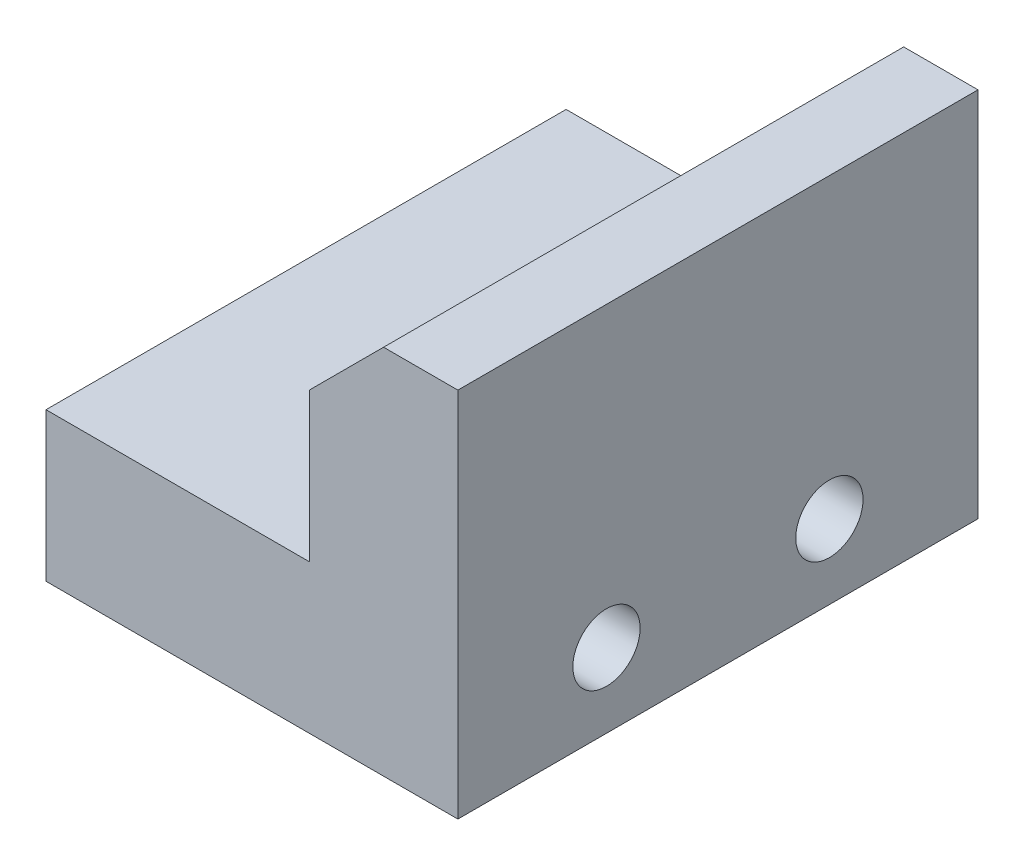
SolidWorks part; units mm, degrees
material "PETG"
ref_plane "Front Plane" through (0, 0, 0) normal (0, 0, 1) x (1, 0, 0)
ref_plane "Top Plane" through (0, 0, 0) normal (0, 1, 0) x (1, 0, 0)
ref_plane "Right Plane" through (0, 0, 0) normal (1, 0, 0) x (0, 0, -1)
sketch "Sketch1" plane through (0, 0, 0) normal (0, 0, 1) x (1, 0, 0)
  line L0 (70.4, 63.5) -> (45, 38.1)
  line L1 (0, -12.7) -> (70.4, -12.7)
  line L2 (0, -12.7) -> (0, 12.7)
  line L3 (0, 12.7) -> (45, 12.7)
  line L5 (45, 63.5) -> (70.4, 63.5)
  line L6 (45, 63.5) -> (45, 12.7)
  line L8 (70.4, 63.5) -> (70.4, -12.7)
  line L9 (57.7, 50.8) -> (70.4, 50.8)
  dimension "D1" = 25.4
  dimension "D2" = 70.4
  dimension "D3" = 25.4
  dimension "D4" = 50.8
  dimension "D5" = 25.4
  dimension "D6" = 12.7
extrude "Boss-Extrude1" add sketch "Sketch1" along normal mid plane 88.9 contours L8 L0 L6 L3 L2 L1 region at (42.9161, 10.0814, 0)
sketch "Sketch2" plane through (70.4, 0, 0) normal (1, 0, 0) x (0, 0, -1)
  line L0 (-19.05, 0) -> (0, 0) construction
  line L1 (0, 0) -> (19.05, 0) construction
  line L2 (-44.45, 50.8) -> (-44.45, -12.7) construction
  circle A0 centre (-19.05, 0) radius 3.25
  circle A1 centre (19.05, 0) radius 3.25
  dimension "D1" = 6.5
  dimension "D2" = 25.4
extrude "Cut-Extrude1" cut sketch "Sketch2" against normal through all
sketch "Sketch3" plane through (70.4, 0, 0) normal (1, 0, 0) x (0, 0, -1)
  circle A0 centre (-19.05, 0) radius 5.75
  circle A1 centre (19.05, 0) radius 5.75
  dimension "D1" = 11.5
extrude "Cut-Extrude2" cut sketch "Sketch3" against normal offset from surface (60.4 mm away) 10 up to face at (0, 0, 15.8)
equation "\"D2@Sketch1\"= 45mm + 1in"
